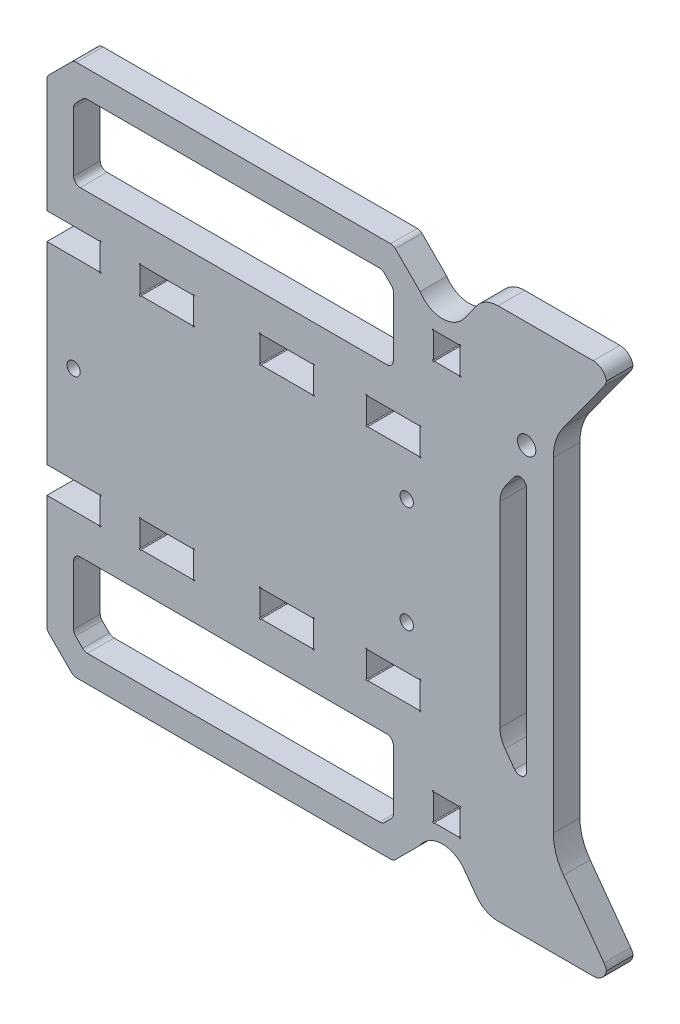
SolidWorks part; units mm, degrees
ref_plane "Front Plane" through (0, 0, 0) normal (0, 0, 1) x (1, 0, 0)
ref_plane "Top Plane" through (0, 0, 0) normal (0, 1, 0) x (1, 0, 0)
ref_plane "Right Plane" through (0, 0, 0) normal (1, 0, 0) x (0, 0, -1)
sketch "Sketch1" plane through (0, 0, 0) normal (0, 0, 1) x (1, 0, 0)
  line L0 (83.672, 0) -> (-43.8164, 0) construction
  line L1 (10.525, 38.1) -> (10.525, -38.1) construction
  line L2 (-27.575, 38.1) -> (48.625, 38.1)
  line L3 (99.425, -63.5) -> (99.425, -60.325)
  line L4 (99.425, -60.325) -> (74.025, -25.4)
  line L5 (-27.575, -63.5) -> (48.625, -63.5)
  line L6 (-27.575, 38.1) -> (-27.575, 54.5197)
  line L7 (48.625, 38.1) -> (48.625, 54.5197)
  line L8 (-24.9447, 57.15) -> (45.9947, 57.15)
  line L9 (-27.575, 63.5) -> (48.625, 63.5)
  line L10 (-33.925, 57.15) -> (-33.925, -57.15)
  line L11 (-27.575, 63.5) -> (-33.925, 57.15)
  line L12 (-24.9447, 57.15) -> (-27.575, 54.5197)
  line L13 (99.425, 63.5) -> (99.425, 60.325)
  line L14 (-23.0849, 59.0099) -> (-29.4349, 52.6599) construction
  line L15 (99.425, 60.325) -> (74.025, 25.4)
  line L16 (74.025, 25.4) -> (74.025, -25.4)
  line L17 (48.625, -38.1) -> (48.625, -54.5197)
  line L18 (-27.575, -38.1) -> (48.625, -38.1)
  line L19 (-24.9447, -57.15) -> (45.9947, -57.15)
  line L20 (-24.9447, -57.15) -> (-27.575, -54.5197)
  line L21 (-27.575, -38.1) -> (-27.575, -54.5197)
  line L22 (-27.575, -63.5) -> (-33.925, -57.15)
  line L23 (48.625, -63.5) -> (54.975, -57.15)
  line L24 (48.625, 63.5) -> (54.975, 57.15)
  line L25 (70.3271, -63.5) -> (99.425, -63.5)
  line L26 (45.9947, 57.15) -> (48.625, 54.5197)
  line L27 (45.9947, -57.15) -> (48.625, -54.5197)
  line L28 (70.3271, 63.5) -> (65.7089, 57.15)
  line L29 (70.3271, 63.5) -> (99.425, 63.5)
  line L30 (78.8831, 75.2646) -> (53.4831, 40.3396) construction
  line L31 (54.975, -42.3909) -> (54.975, -57.15)
  line L32 (70.3271, -63.5) -> (65.7089, -57.15)
  line L34 (48.625, -63.5) -> (54.975, -57.15)
  line L35 (65.7089, 57.15) -> (54.975, 42.3909)
  line L36 (54.975, 42.3909) -> (54.975, 57.15)
  line L37 (65.7089, -57.15) -> (54.975, -42.3909)
  point P7 (-27.575, 0)
  point P21 (74.025, 0)
  point P22 (-33.925, 0)
  dimension "D1" = 25.4
  dimension "D2" = 76.2
  dimension "D3" = 127
  dimension "D4" = 6.35
  dimension "D7" = 3.175
  dimension "D8" = 25.4
  dimension "D9" = 25.4
  dimension "D6" = 6.35
extrude "Boss-Extrude1" add sketch "Sketch1" along normal blind 6.35 contours L23 L32 L25 L3 L4 L16 L15 L13 L29 L28 L24 L9 L11 L10 L22 L5 L8 L26 L7 L2 L6 L12 L27 L19 L20 L21 L18 L17 region at (27.1557, 0, 0)
fillet "Fillet1" radius 6.35 4 edges at (70.3271, 63.5, 3.175) (70.3271, -63.5, 3.175) (54.975, -42.3909, 3.175) (54.975, 42.3909, 3.175)
fillet "Fillet3" radius 3.175 4 edges at (99.425, 63.5, 3.175) (99.425, 60.325, 3.175) (99.425, -60.325, 3.175) (99.425, -63.5, 3.175)
fillet "Fillet4" radius 6.35 2 edges at (74.025, -25.4, 3.175) (74.025, 25.4, 3.175)
fillet "Fillet7" radius 1.5875 4 edges at (-27.575, -38.1, 3.175) (48.625, -38.1, 3.175) (48.625, 38.1, 3.175) (-27.575, 38.1, 3.175)
fillet "Fillet8" radius 1.5875 6 edges at (-33.925, -57.15, 3.175) (-27.575, -63.5, 3.175) (48.625, -63.5, 3.175) (48.625, 63.5, 3.175) (-27.575, 63.5, 3.175) (-33.925, 57.15, 3.175)
fillet "Fillet9" radius 1.5875 8 edges at (-27.575, 54.5197, 3.175) (-24.9447, 57.15, 3.175) (-27.575, -54.5197, 3.175) (-24.9447, -57.15, 3.175) (45.9947, -57.15, 3.175) (48.625, -54.5197, 3.175) (48.625, 54.5197, 3.175) (45.9947, 57.15, 3.175)
sketch "Sketch2" plane through (0, 0, 6.35) normal (0, 0, 1) x (1, 0, 0)
  line L0 (-33.925, 0) -> (74.025, 0) construction
  line L1 (-33.925, 56.4924) -> (-33.925, -56.4924) construction
  line L2 (74.025, 23.3351) -> (74.025, -23.3351) construction
  line L3 (48.625, 39.6875) -> (48.625, 53.8622) construction
  line L4 (58.3484, 50.8) -> (64.3016, 50.8)
  line L5 (58.15, 50.6016) -> (58.15, 44.6484)
  line L6 (58.3484, 44.45) -> (64.3016, 44.45)
  line L7 (64.5, 50.6016) -> (64.5, 44.6484)
  line L8 (64.5, -50.6016) -> (64.5, -44.6484)
  line L9 (58.3484, -50.8) -> (64.3016, -50.8)
  line L10 (58.15, -50.6016) -> (58.15, -44.6484)
  line L11 (58.3484, -44.45) -> (64.3016, -44.45)
  arc A0 (58.3484, 50.8) -> (58.15, 50.6016) centre (58.15, 50.8) ccw
  arc A1 (64.5, 50.6016) -> (64.3016, 50.8) centre (64.5, 50.8) ccw
  arc A2 (64.3016, 44.45) -> (64.5, 44.6484) centre (64.5, 44.45) ccw
  arc A3 (58.15, 44.6484) -> (58.3484, 44.45) centre (58.15, 44.45) ccw
  arc A4 (64.3016, -44.45) -> (64.5, -44.6484) centre (64.5, -44.45) cw
  arc A5 (64.5, -50.6016) -> (64.3016, -50.8) centre (64.5, -50.8) cw
  arc A6 (58.3484, -50.8) -> (58.15, -50.6016) centre (58.15, -50.8) cw
  arc A7 (58.15, -44.6484) -> (58.3484, -44.45) centre (58.15, -44.45) cw
  point P10 (48.625, 46.7748)
  dimension "D5" = 0.3969
  dimension "D6" = 0.3969
  dimension "D7" = 0.3969
  dimension "D8" = 0.3969
  dimension "D1" = 6.35
  dimension "D2" = 6.35
  dimension "D3" = 50.8
  dimension "D4" = 9.525
extrude "Cut-Extrude1" cut sketch "Sketch2" against normal through all
sketch "Sketch5" plane through (0, 0, 6.35) normal (0, 0, 1) x (1, 0, 0)
  line L0 (-33.925, 29.3675) -> (74.025, 29.3675) construction
  line L1 (-33.925, 56.4924) -> (-33.925, -56.4924) construction
  line L2 (74.025, 23.3351) -> (74.025, -23.3351) construction
  line L3 (-25.9875, 38.1) -> (47.0375, 38.1) construction
  line L4 (-33.925, 23.0175) -> (74.025, 23.0175) construction
  line L5 (-33.925, 0) -> (74.025, 0) construction
  line L6 (-11.5016, 29.3675) -> (0.8016, 29.3675)
  line L7 (-11.7, 29.169) -> (-11.7, 23.2159)
  line L8 (-11.5016, 23.0175) -> (0.8016, 23.0175)
  line L9 (1, 29.169) -> (1, 23.2159)
  line L10 (42.4734, 29.3675) -> (54.7766, 29.3675)
  line L11 (42.275, 29.169) -> (42.275, 23.2159)
  line L12 (42.4734, 23.0175) -> (54.7766, 23.0175)
  line L13 (54.975, 29.169) -> (54.975, 23.2159)
  line L14 (29.3766, 29.3675) -> (17.0734, 29.3675)
  line L15 (29.575, 29.169) -> (29.575, 23.2159)
  line L16 (29.3766, 23.0175) -> (17.0734, 23.0175)
  line L17 (16.875, 29.169) -> (16.875, 23.2159)
  line L18 (-21.4234, 29.3675) -> (-33.925, 29.3675)
  line L19 (-21.225, 29.169) -> (-21.225, 23.2159)
  line L20 (-21.4234, 23.0175) -> (-33.925, 23.0175)
  line L21 (-33.925, 29.3675) -> (-33.925, 23.0175)
  line L22 (-33.925, -29.3675) -> (-33.925, -23.0175)
  line L23 (-21.4234, -23.0175) -> (-33.925, -23.0175)
  line L24 (-21.225, -29.169) -> (-21.225, -23.2159)
  line L25 (-21.4234, -29.3675) -> (-33.925, -29.3675)
  line L26 (16.875, -29.169) -> (16.875, -23.2159)
  line L27 (29.3766, -23.0175) -> (17.0734, -23.0175)
  line L28 (29.575, -29.169) -> (29.575, -23.2159)
  line L29 (29.3766, -29.3675) -> (17.0734, -29.3675)
  line L30 (54.975, -29.169) -> (54.975, -23.2159)
  line L31 (42.4734, -23.0175) -> (54.7766, -23.0175)
  line L32 (42.275, -29.169) -> (42.275, -23.2159)
  line L33 (42.4734, -29.3675) -> (54.7766, -29.3675)
  line L34 (1, -29.169) -> (1, -23.2159)
  line L35 (-11.5016, -23.0175) -> (0.8016, -23.0175)
  line L36 (-11.7, -29.169) -> (-11.7, -23.2159)
  line L37 (-11.5016, -29.3675) -> (0.8016, -29.3675)
  line L38 (-33.925, 26.1925) -> (54.975, 26.1925) construction
  arc A0 (-21.225, 29.169) -> (-21.4234, 29.3675) centre (-21.225, 29.3675) ccw
  arc A1 (-11.5016, 29.3675) -> (-11.7, 29.169) centre (-11.7, 29.3675) ccw
  arc A2 (1, 29.169) -> (0.8016, 29.3675) centre (1, 29.3675) ccw
  arc A3 (29.575, 29.169) -> (29.3766, 29.3675) centre (29.575, 29.3675) ccw
  arc A4 (17.0734, 29.3675) -> (16.875, 29.169) centre (16.875, 29.3675) ccw
  arc A5 (54.975, 29.169) -> (54.7766, 29.3675) centre (54.975, 29.3675) ccw
  arc A6 (42.4734, 29.3675) -> (42.275, 29.169) centre (42.275, 29.3675) ccw
  arc A7 (17.0734, 23.0175) -> (16.875, 23.2159) centre (16.875, 23.0175) cw
  arc A8 (29.575, 23.2159) -> (29.3766, 23.0175) centre (29.575, 23.0175) cw
  arc A9 (42.4734, 23.0175) -> (42.275, 23.2159) centre (42.275, 23.0175) cw
  arc A10 (54.975, 23.2159) -> (54.7766, 23.0175) centre (54.975, 23.0175) cw
  arc A11 (1, 23.2159) -> (0.8016, 23.0175) centre (1, 23.0175) cw
  arc A12 (-11.5016, 23.0175) -> (-11.7, 23.2159) centre (-11.7, 23.0175) cw
  arc A13 (-21.225, 23.2159) -> (-21.4234, 23.0175) centre (-21.225, 23.0175) cw
  arc A14 (-21.225, -23.2159) -> (-21.4234, -23.0175) centre (-21.225, -23.0175) ccw
  arc A15 (-11.5016, -23.0175) -> (-11.7, -23.2159) centre (-11.7, -23.0175) ccw
  arc A16 (1, -23.2159) -> (0.8016, -23.0175) centre (1, -23.0175) ccw
  arc A17 (54.975, -23.2159) -> (54.7766, -23.0175) centre (54.975, -23.0175) ccw
  arc A18 (42.4734, -23.0175) -> (42.275, -23.2159) centre (42.275, -23.0175) ccw
  arc A19 (29.575, -23.2159) -> (29.3766, -23.0175) centre (29.575, -23.0175) ccw
  arc A20 (17.0734, -23.0175) -> (16.875, -23.2159) centre (16.875, -23.0175) ccw
  arc A21 (42.4734, -29.3675) -> (42.275, -29.169) centre (42.275, -29.3675) cw
  arc A22 (54.975, -29.169) -> (54.7766, -29.3675) centre (54.975, -29.3675) cw
  arc A23 (17.0734, -29.3675) -> (16.875, -29.169) centre (16.875, -29.3675) cw
  arc A24 (29.575, -29.169) -> (29.3766, -29.3675) centre (29.575, -29.3675) cw
  arc A25 (1, -29.169) -> (0.8016, -29.3675) centre (1, -29.3675) cw
  arc A26 (-11.5016, -29.3675) -> (-11.7, -29.169) centre (-11.7, -29.3675) cw
  arc A27 (-21.225, -29.169) -> (-21.4234, -29.3675) centre (-21.225, -29.3675) cw
  dimension "D11" = 0.3969
  dimension "D12" = 0.3969
  dimension "D13" = 0.3969
  dimension "D14" = 0.3969
  dimension "D15" = 0.3969
  dimension "D16" = 0.3969
  dimension "D17" = 0.3969
  dimension "D1" = 8.7325
  dimension "D3" = 12.7
  dimension "D4" = 12.7
  dimension "D5" = 41.275
  dimension "D6" = 34.925
  dimension "D7" = 12.7
  dimension "D8" = 12.7
  dimension "D9" = 50.8
  dimension "D10" = 0
  dimension "D2" = 6.35
extrude "Cut-Extrude4" cut sketch "Sketch5" against normal through all
sketch "Sketch6" plane through (0, 0, 6.35) normal (0, 0, 1) x (1, 0, 0)
  line L0 (80.375, 34.1312) -> (80.375, -34.1312)
  line L1 (98.8177, 59.49) -> (75.2395, 27.07) construction
  line L2 (98.8177, -59.49) -> (75.2395, -27.07) construction
  line L3 (74.025, 23.3351) -> (74.025, -23.3351) construction
  line L4 (86.725, 34.1312) -> (86.725, -34.1312)
  line L5 (86.725, 34.1312) -> (86.725, 42.8625)
  line L6 (86.725, 42.8625) -> (80.375, 34.1312)
  line L7 (86.725, -34.1312) -> (86.725, -42.8625)
  line L8 (86.725, -42.8625) -> (80.375, -34.1312)
  dimension "D1" = 6.35
  dimension "D2" = 6.35
extrude "Boss-Extrude2" add sketch "Sketch6" against normal blind 6.35
fillet "Fillet10" radius 1.5875 2 edges at (80.375, -34.1312, 3.175) (80.375, 34.1312, 3.175)
fillet "Fillet11" radius 12.7 2 edges at (86.725, 42.8625, 3.175) (86.725, -42.8625, 3.175)
hole_wizard "11/64 (0.17188) Diameter Hole1" positions "Sketch8" profile "Sketch7" hole size "11/64" standard "ANSI Inch" end condition through all
sketch "Sketch8" plane through (0, 0, 6.35) normal (0, 0, 1) x (1, 0, 0)
  line L1 (-33.925, -29.3675) -> (-33.925, -56.4924) construction
  line L2 (73.5606, 63.5) -> (96.25, 63.5) construction
  point P0 (80.375, 38.1)
  dimension "D1" = 25.4
  dimension "D2" = 114.3
sketch "Sketch7" plane through (80.375, 38.1, 6.35) normal (1, 0, 0) x (0, -1, 0)
  line L0 (0, 0) -> (0, 6.35)
  line L1 (0, 6.35) -> (2.1829, 6.35)
  line L2 (2.1829, 6.35) -> (2.1829, 0)
  line L5 (2.1829, 0) -> (0, 0)
  line L11 (0, -6.35) -> (0, 107.95) construction
  dimension "Thru Hole Dia." = 4.3658
  dimension "Thru Hole Depth" = 6.35
sketch "Sketch10" plane through (0, 0, 6.35) normal (0, 0, 1) x (1, 0, 0)
  line L0 (51.8, 63.5) -> (51.8, -63.5) construction
  line L1 (-26.9174, 63.5) -> (47.9674, 63.5) construction
  line L2 (-26.9174, -63.5) -> (47.9674, -63.5) construction
  line L3 (23.225, 29.3675) -> (23.225, -29.3675) construction
  line L4 (29.3766, 29.3675) -> (17.0734, 29.3675) construction
  line L5 (17.0734, -29.3675) -> (29.3766, -29.3675) construction
  line L6 (-27.575, 63.5) -> (-27.575, -63.5) construction
  line L7 (-33.925, 0) -> (74.025, 0) construction
  line L8 (-33.925, 23.0175) -> (-33.925, -23.0175) construction
  line L9 (74.025, 23.3351) -> (74.025, -23.3351) construction
  circle A0 centre (51.8, 12.7) radius 1.5875
  circle A1 centre (51.8, -12.7) radius 1.5875
  circle A2 centre (-27.575, 0) radius 1.5875
  dimension "D3" = 3.175
  dimension "D5" = 79.375
  dimension "D1" = 28.575
  dimension "D2" = 79.375
  dimension "D4" = 12.7
extrude "Cut-Extrude6" cut sketch "Sketch10" against normal through all
